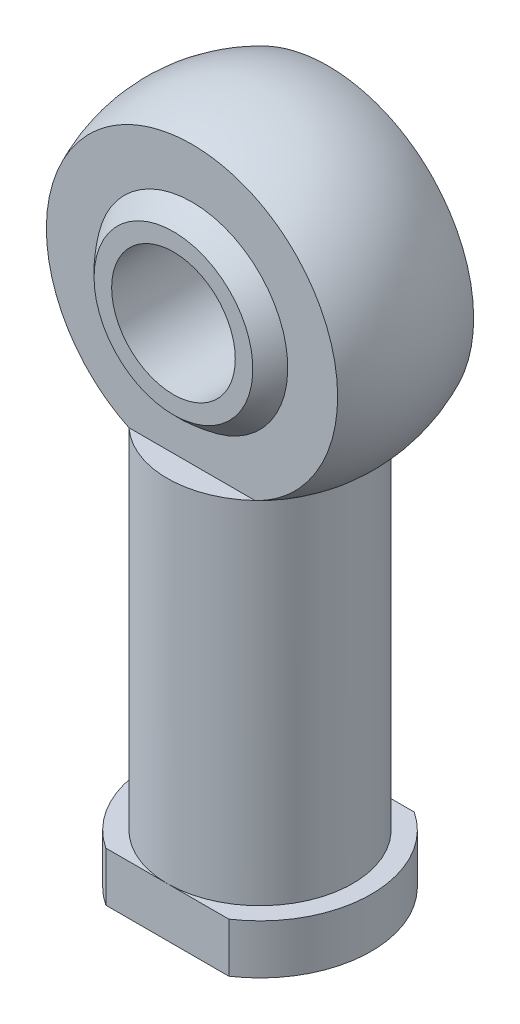
SolidWorks part; units mm, degrees
ref_plane "Front Plane" through (0, 0, 0) normal (0, 0, 1) x (1, 0, 0)
ref_plane "Top Plane" through (0, 0, 0) normal (0, 1, 0) x (1, 0, 0)
ref_plane "Right Plane" through (0, 0, 0) normal (1, 0, 0) x (0, 0, -1)
sketch "Sketch1" plane through (0, 0, 0) normal (0, 0, 1) x (1, 0, 0)
  line L0 (0, 0) -> (0, 43) construction
  line L1 (-7.5, 4) -> (-7.5, 32.3816)
  line L2 (-7.5, 4) -> (-9, 4)
  line L3 (-9, 4) -> (-9, 0)
  line L4 (-9, 0) -> (0, 0)
  line L5 (0, 0) -> (0, 56)
  circle A0 centre (0, 43) radius 9.5
  circle A1 centre (0, 43) radius 10.5
  circle A2 centre (0, 43) radius 13
  dimension "D2" = 26
  dimension "D3" = 21
  dimension "D4" = 19
  dimension "D1" = 43
  dimension "D5" = 15
  dimension "D6" = 18
  dimension "D7" = 4
revolve "Revolve5" add sketch "Sketch1" angle 360 about L0 region at (-0.2348, 53, 0)
revolve "Revolve6" add sketch "Sketch1<7>" angle 360 about L0 region at (-3.9102, 15.0497, 0) region at (-12.1132, 46.8466, 0)
sketch "Sketch1<7>" plane through (0, 0, 0) normal (0, 0, 1) x (1, 0, 0) same geometry as "Sketch1"
sketch "Sketch3" plane through (0, 0, 0) normal (1, 0, 0) x (0, 0, -1)
  line L0 (0, 0) -> (0, 56) construction
  line L1 (-23.0793, 62.8909) -> (-5.5, 62.8909)
  line L2 (-23.0793, 62.8909) -> (-23.0793, 32.3816)
  line L3 (-23.0793, 32.3816) -> (-5.5, 32.3816)
  line L4 (-5.5, 62.8909) -> (-5.5, 32.3816)
  line L5 (0, 0) -> (0, 56) construction
  line L6 (7.5, 32.3816) -> (-7.5, 32.3816) construction
  line L7 (23.0793, 32.3816) -> (5.5, 32.3816)
  line L8 (5.5, 62.8909) -> (5.5, 32.3816)
  line L9 (23.0793, 62.8909) -> (5.5, 62.8909)
  line L10 (23.0793, 62.8909) -> (23.0793, 32.3816)
  dimension "D1" = 11
extrude "Cut-Extrude3" cut sketch "Sketch3" against normal through all both and the other way through all
revolve "Revolve7" add sketch "Sketch1<8>" angle 360 about L0 region at (-4.0319, 43, 0)
sketch "Sketch1<8>" plane through (0, 0, 0) normal (0, 0, 1) x (1, 0, 0) same geometry as "Sketch1"
sketch "Sketch4" plane through (0, 0, 0) normal (1, 0, 0) x (0, 0, -1)
  line L0 (0, 56) -> (0, 30) construction
  line L1 (-21.9327, 55.3399) -> (-7, 55.3399)
  line L2 (-21.9327, 55.3399) -> (-21.9327, 35.4641)
  line L3 (-21.9327, 35.4641) -> (-7, 35.4641)
  line L4 (-7, 55.3399) -> (-7, 35.4641)
  line L5 (0, 56) -> (0, 30) construction
  line L6 (21.9327, 35.4641) -> (7, 35.4641)
  line L7 (7, 55.3399) -> (7, 35.4641)
  line L8 (21.9327, 55.3399) -> (7, 55.3399)
  line L9 (21.9327, 55.3399) -> (21.9327, 35.4641)
  dimension "D1" = 14
extrude "Cut-Extrude4" cut sketch "Sketch4" against normal through all both and the other way through all
sketch "Sketch5" plane through (0, 0, 7) normal (0, 0, 1) x (1, 0, 0)
  circle A0 centre (0, 43) radius 5
  dimension "D1" = 10
extrude "Cut-Extrude5" cut sketch "Sketch5" against normal through all both and the other way through all
sketch "Sketch6" plane through (0, 0, 0) normal (0, 1, 0) x (1, 0, 0)
  line L0 (-15.9573, 0) -> (23.5227, 0) construction
  line L1 (-7.5611, 12.7928) -> (8.4336, 12.7928)
  line L2 (-7.5611, 12.7928) -> (-7.5611, 7.5)
  line L3 (-7.5611, 7.5) -> (8.4336, 7.5)
  line L4 (8.4336, 12.7928) -> (8.4336, 7.5)
  line L5 (-7.5611, -7.5) -> (8.4336, -7.5)
  line L6 (8.4336, -12.7928) -> (8.4336, -7.5)
  line L7 (-7.5611, -12.7928) -> (8.4336, -12.7928)
  line L8 (-7.5611, -12.7928) -> (-7.5611, -7.5)
  circle A0 centre (0, 0) radius 7.5 construction
extrude "Cut-Extrude6" cut sketch "Sketch6" along normal through all both and the other way through all
